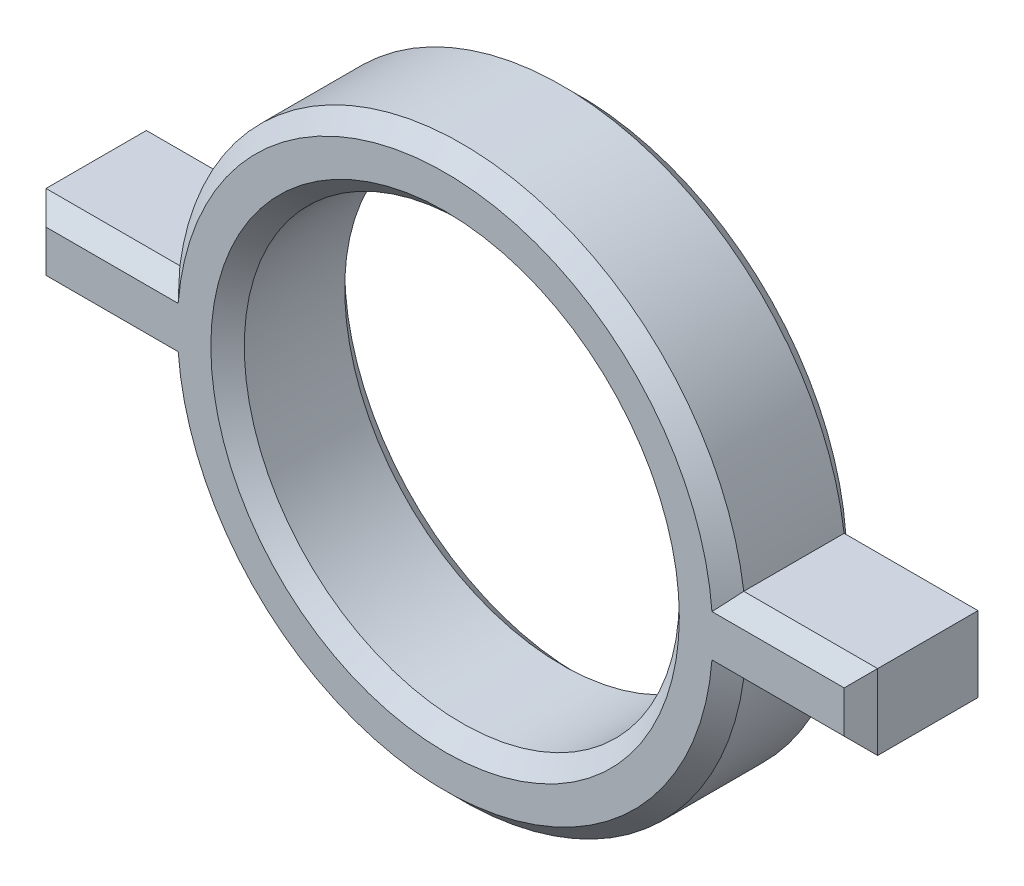
SolidWorks part; units mm, degrees
material "PLA"
ref_plane "Front Plane" through (0, 0, 0) normal (0, 0, 1) x (1, 0, 0)
ref_plane "Top Plane" through (0, 0, 0) normal (0, 1, 0) x (1, 0, 0)
ref_plane "Right Plane" through (0, 0, 0) normal (1, 0, 0) x (0, 0, -1)
sketch "Sketch1" plane through (0, 0, 0) normal (0, 0, 1) x (1, 0, 0)
  line L0 (-12.4252, 1.125) -> (-12.4252, -1.125) construction
  line L1 (-12.4252, -1.125) -> (-8.4252, -1.125) construction
  line L2 (-8.4252, 1.125) -> (-12.4252, 1.125) construction
  line L3 (8.4252, -1.125) -> (12.4252, -1.125) construction
  line L4 (12.4252, -1.125) -> (12.4252, 1.125) construction
  line L5 (12.4252, 1.125) -> (8.4252, 1.125) construction
  line L6 (8.4252, -1.125) -> (12.4252, -1.125)
  line L7 (12.4252, -1.125) -> (12.4252, 1.125)
  line L8 (12.4252, 1.125) -> (8.4252, 1.125)
  line L9 (-12.4252, 1.125) -> (-12.4252, -1.125)
  line L10 (-8.4252, 1.125) -> (-12.4252, 1.125)
  line L11 (-12.4252, -1.125) -> (-8.4252, -1.125)
  arc A0 (-8.4252, -1.125) -> (8.4252, -1.125) centre (0, 0) ccw construction
  circle A1 centre (0, 0) radius 6.5 construction
  arc A3 (8.4252, 1.125) -> (-8.4252, 1.125) centre (0, 0) ccw construction
  arc A4 (8.4252, 1.125) -> (-8.4252, 1.125) centre (0, 0) ccw
  arc A5 (-8.4252, -1.125) -> (8.4252, -1.125) centre (0, 0) ccw
  circle A6 centre (0, 0) radius 6.5
extrude "Boss-Extrude1" add sketch "Sketch1" along normal blind 4
chamfer "Chamfer1" distance 0.5 angle 45 18 edges at (6.5, 0, 0) (-12.4252, 0, 0) (-10.4252, -1.125, 0) (0, -8.5, 0) (10.4252, -1.125, 0) (12.4252, 0, 0) (10.4252, 1.125, 0) (0, 8.5, 0) (-10.4252, 1.125, 0) (6.5, 0, 4) (0, 8.5, 4) (10.4252, 1.125, 4) (12.4252, 0, 4) (10.4252, -1.125, 4) (0, -8.5, 4) (-10.4252, -1.125, 4) (-12.4252, 0, 4) (-10.4252, 1.125, 4)
